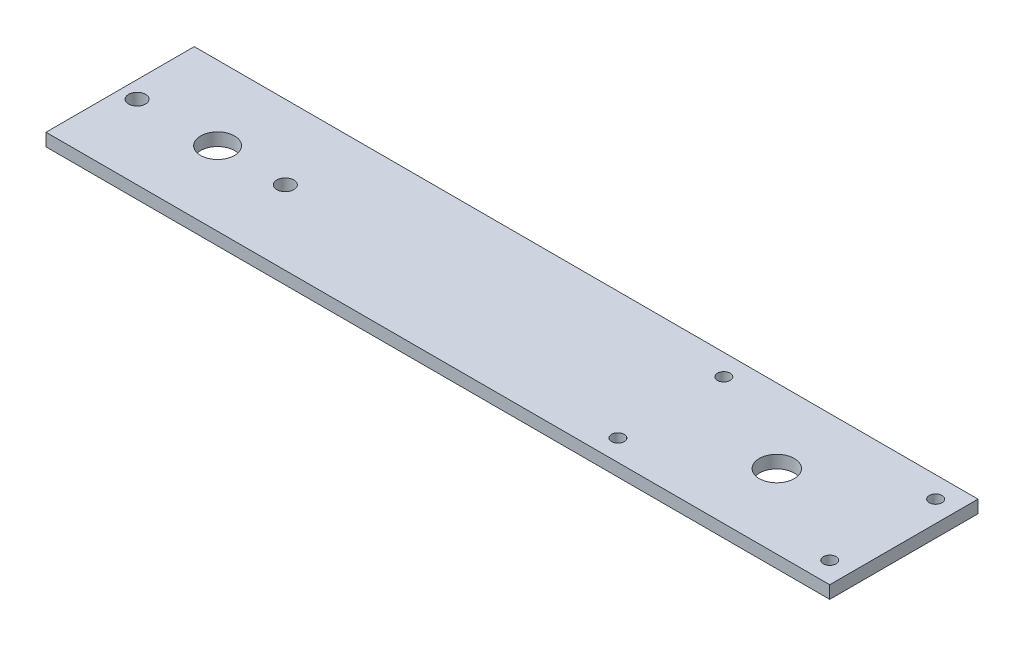
SolidWorks part; units mm, degrees
ref_plane "Front Plane" through (0, 0, 0) normal (0, 0, 1) x (1, 0, 0)
ref_plane "Top Plane" through (0, 0, 0) normal (0, 1, 0) x (1, 0, 0)
ref_plane "Right Plane" through (0, 0, 0) normal (1, 0, 0) x (0, 0, -1)
sketch "Sketch1" plane through (0, 0, 0) normal (0, 1, 0) x (1, 0, 0)
  line L1 (-92.5, 17.5) -> (92.5, 17.5)
  line L2 (-92.5, 17.5) -> (-92.5, -17.5)
  line L3 (-92.5, -17.5) -> (92.5, -17.5)
  line L4 (92.5, 17.5) -> (92.5, -17.5)
  line L5 (-92.5, 17.5) -> (92.5, -17.5) construction
  line L6 (-92.5, -17.5) -> (92.5, 17.5) construction
  circle A4 centre (62.5, 0) radius 4.125
  circle A5 centre (-69.5, 0) radius 4
  circle A8 centre (-88.5, 0) radius 2
  circle A9 centre (-53.5, 0) radius 2
  point P0 (0, 0)
  point P17 (92.5, 0)
  dimension "D3" = 30
  dimension "D4" = 17.5
  dimension "D5" = 8
  dimension "D6" = 8.25
  dimension "D7" = 17.5
  dimension "D8" = 23
  dimension "D1" = 35
  dimension "D2" = 185
extrude "Boss-Extrude1" add sketch "Sketch1" along normal blind 3
sketch "Sketch2" plane through (0, 3, 0) normal (0, 1, 0) x (1, 0, 0)
  line L0 (-92.5, 17.5) -> (-92.5, -17.5) construction
  line L1 (-92.5, -17.5) -> (92.5, -17.5) construction
  line L2 (-115.5, 6.5) -> (-115.5, -6.7467) construction
  circle A0 centre (-115.5, 6.5) radius 3
  circle A1 centre (-115.5, 6.5) radius 31 construction
  circle A2 centre (-27, 6.5) radius 57.5 construction
  circle A3 centre (-133, -0.5) radius 2
  circle A4 centre (-98, -0.5) radius 2
  dimension "D1" = 6
  dimension "D3" = 24
  dimension "D4" = 7
  dimension "D2" = 23
  dimension "D5" = 17.5
extrude "Cut-Extrude1" [suppressed] cut sketch "Sketch2" against normal through all contours A3 | A4
sketch "Sketch3" plane through (0, 3, 0) normal (0, 1, 0) x (1, 0, 0)
  line L0 (-92.5, -17.5) -> (92.5, -17.5) construction
  line L3 (92.5, 17.5) -> (92.5, -17.5) construction
  line L4 (-55, 0) -> (55, 0) construction
  circle A0 centre (72.5, -9.5) radius 1.5
  circle A3 centre (72.5, 9.5) radius 1.5
  dimension "D1" = 3
  dimension "D2" = 8
  dimension "D3" = 20
extrude "Cut-Extrude2" [suppressed] cut sketch "Sketch3" against normal through all
sketch "Sketch4" plane through (0, 3, 0) normal (0, 1, 0) x (1, 0, 0)
  line L0 (-92.5, 17.5) -> (92.5, 17.5) construction
  line L1 (62.5, 0) -> (41.5, 0) construction
  line L2 (92.5, 17.5) -> (92.5, -17.5) construction
  line L3 (-55, 0) -> (55, 0) construction
  circle A1 centre (52.5, 9.5) radius 1.5
  circle A2 centre (52.5, -9.5) radius 1.5
  dimension "D2" = 8
  dimension "D4" = 3
  dimension "D1" = 21
  dimension "D3" = 40
extrude "Cut-Extrude3" [suppressed] cut sketch "Sketch4" against normal through all
sketch "Sketch5" plane through (0, 3, 0) normal (0, 1, 0) x (1, 0, 0)
  line L0 (-61.8339, 5.2781) -> (-77.04, -21.0597) construction
  line L1 (-92.5, 17.5) -> (-92.5, -17.5) construction
  circle A0 centre (-69.5, 0) radius 4 construction
  circle A1 centre (-58.8075, 10.52) radius 1.5
  circle A2 centre (-73.2643, -14.52) radius 1.5
  dimension "D1" = 3
  dimension "D2" = 3
  dimension "D4" = 15
  dimension "D5" = 15
  dimension "D3" = 30
extrude "Cut-Extrude5" [suppressed] cut sketch "Sketch5" against normal through all
sketch "Sketch6" plane through (0, 3, 0) normal (0, 1, 0) x (1, 0, 0)
  line L0 (-92.5, 17.5) -> (92.5, 17.5) construction
  line L1 (92.5, 17.5) -> (92.5, -17.5) construction
  line L2 (-1.65, 0) -> (1.65, 0) construction
  line L3 (62.5, 0) -> (62.5, 14.7754) construction
  circle A0 centre (87.5, 12.5) radius 1.5
  circle A1 centre (87.5, -12.5) radius 1.5
  circle A2 centre (37.5, -12.5) radius 1.5
  circle A3 centre (37.5, 12.5) radius 1.5
  dimension "D3" = 3
  dimension "D1" = 5
  dimension "D2" = 5
extrude "Cut-Extrude6" cut sketch "Sketch6" against normal through all
sketch "Sketch7" plane through (0, 3, 0) normal (0, 1, 0) x (1, 0, 0)
  line L1 (62.5, 0) -> (87.5, 0)
  line L2 (62.5, 0) -> (62.5, 12.5)
  line L3 (62.5, 12.5) -> (87.5, 12.5)
  line L4 (87.5, 0) -> (87.5, 12.5)
